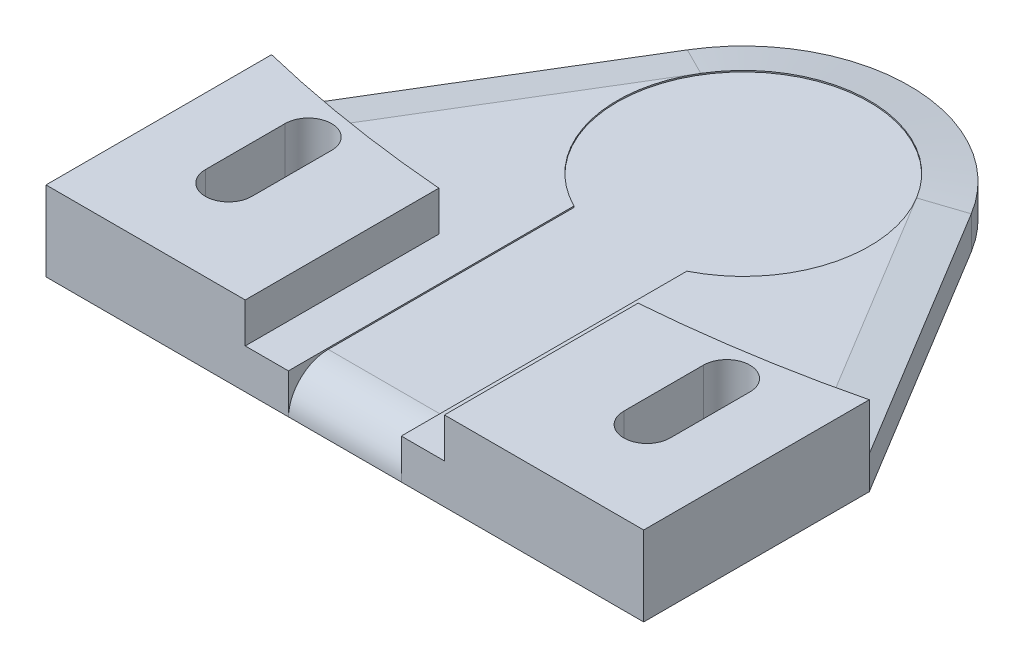
SolidWorks part; units mm, degrees
ref_plane "Front Plane" through (0, 0, 0) normal (0, 0, 1) x (1, 0, 0)
ref_plane "Top Plane" through (0, 0, 0) normal (0, 1, 0) x (1, 0, 0)
ref_plane "Right Plane" through (0, 0, 0) normal (1, 0, 0) x (0, 0, -1)
sketch "Sketch1" plane through (0, 0, 0) normal (0, 1, 0) x (1, 0, 0)
  line L0 (-10.1, 97.6) -> (-5.1, 97.6) construction
  line L1 (-9.1, 105.2) -> (-3.5, 105.2) construction
  line L2 (-10.1, 104.2) -> (-10.1, 97.6) construction
  line L3 (-9.1, 85) -> (-3.5, 85) construction
  line L4 (10.1, 104.2) -> (10.1, 97.6) construction
  line L5 (-5.1, 97.6) -> (-5.1, 92.6) construction
  line L6 (-5.1, 92.6) -> (-10.1, 92.6) construction
  line L7 (-10.1, 92.6) -> (-10.1, 86) construction
  line L8 (10.1, 97.6) -> (5.1, 97.6) construction
  line L9 (5.1, 97.6) -> (5.1, 92.6) construction
  line L10 (5.1, 92.6) -> (10.1, 92.6) construction
  line L11 (10.1, 92.6) -> (10.1, 86) construction
  line L12 (-34.641, 100) -> (-17.3205, 90) construction
  line L13 (0, 80) -> (17.3205, 90) construction
  line L14 (0, 95.1) -> (0, 0) construction
  line L15 (-17.3205, 90) -> (-53.6936, 27) construction
  line L16 (-17.3205, 90) -> (0, 80) construction
  line L17 (17.3205, 90) -> (53.6936, 27) construction
  line L18 (17.3205, 90) -> (34.641, 100) construction
  line L19 (-53.6936, 27) -> (-50.2295, 25) construction
  line L20 (-50.2295, 25) -> (-41.5692, 40) construction
  line L21 (-32.909, 45) -> (32.909, 45) construction
  line L22 (41.5692, 40) -> (50.2295, 25) construction
  line L23 (50.2295, 25) -> (53.6936, 27) construction
  line L24 (-20.4959, 76.5) -> (-32.0429, 56.5) construction
  line L25 (-27.7128, 49) -> (27.7128, 49) construction
  line L26 (32.0429, 56.5) -> (20.4959, 76.5) construction
  line L27 (-16.1658, 79) -> (16.1658, 79) construction
  line L28 (-2.5, 104.2) -> (-2.5, 103.95) construction
  line L29 (-2.5, 103.95) -> (2.5, 103.95) construction
  line L30 (2.5, 103.95) -> (2.5, 104.2) construction
  line L31 (3.5, 105.2) -> (9.1, 105.2) construction
  line L32 (-2.5, 86) -> (-2.5, 86.25) construction
  line L33 (-2.5, 86.25) -> (2.5, 86.25) construction
  line L34 (2.5, 86.25) -> (2.5, 86) construction
  line L35 (3.5, 85) -> (9.1, 85) construction
  line L36 (-34.641, 100) -> (-20.6443, 112.1724) construction
  line L37 (-7.5199, 117.081) -> (7.5199, 117.081) construction
  line L38 (20.6443, 112.1724) -> (34.641, 100) construction
  line L39 (140.292, -127.8992) -> (137.792, -132.2294) construction
  line L40 (146.3738, -132.5653) -> (143.5738, -137.415) construction
  line L41 (146.0078, -131.1992) -> (140.292, -127.8992) construction
  line L42 (128.8801, -122.4653) -> (126.0801, -127.315) construction
  line L43 (135.9078, -148.693) -> (130.192, -145.393) construction
  line L44 (137.792, -132.2294) -> (133.4619, -129.7294) construction
  line L45 (133.4619, -129.7294) -> (135.9619, -125.3992) construction
  line L46 (135.9619, -125.3992) -> (130.2462, -122.0992) construction
  line L47 (130.192, -145.393) -> (132.692, -141.0628) construction
  line L48 (132.692, -141.0628) -> (128.3619, -138.5628) construction
  line L49 (128.3619, -138.5628) -> (125.8619, -142.893) construction
  line L50 (125.8619, -142.893) -> (120.1462, -139.593) construction
  line L51 (154.641, -107.8461) -> (137.3205, -117.8461) construction
  line L52 (120, -127.8461) -> (120, -147.8461) construction
  line L53 (137.3205, -117.8461) -> (100.9474, -54.8461) construction
  line L54 (137.3205, -117.8461) -> (120, -127.8461) construction
  line L55 (120, -147.8461) -> (47.2539, -147.8461) construction
  line L56 (120, -147.8461) -> (120, -167.8461) construction
  line L57 (100.9474, -54.8461) -> (97.4833, -56.8461) construction
  line L58 (97.4833, -56.8461) -> (106.1436, -71.8461) construction
  line L59 (106.1436, -81.8461) -> (73.2346, -138.8461) construction
  line L60 (64.5744, -143.8461) -> (47.2539, -143.8461) construction
  line L61 (47.2539, -143.8461) -> (47.2539, -147.8461) construction
  line L62 (127.2169, -108.3461) -> (115.6699, -88.3461) construction
  line L63 (107.0096, -88.3461) -> (79.2968, -136.3461) construction
  line L64 (83.6269, -143.8461) -> (106.7209, -143.8461) construction
  line L65 (127.2169, -113.3461) -> (111.0511, -141.3461) construction
  line L66 (142.2078, -137.781) -> (141.9913, -137.656) construction
  line L67 (141.9913, -137.656) -> (139.4913, -141.9862) construction
  line L68 (139.4913, -141.9862) -> (139.7078, -142.1112) construction
  line L69 (140.0738, -143.4772) -> (137.2738, -148.3269) construction
  line L70 (126.4462, -128.681) -> (126.6627, -128.806) construction
  line L71 (126.6627, -128.806) -> (124.1627, -133.1362) construction
  line L72 (124.1627, -133.1362) -> (123.9462, -133.0112) construction
  line L73 (122.5801, -133.3772) -> (119.7801, -138.2269) construction
  line L74 (154.641, -107.8461) -> (158.1843, -126.0538) construction
  line L75 (155.873, -139.8742) -> (148.3531, -152.899) construction
  line L76 (137.54, -161.8108) -> (120, -167.8461) construction
  line L77 (-130.192, -145.393) -> (-132.692, -141.0628) construction
  line L78 (-137.2738, -148.3269) -> (-140.0738, -143.4772) construction
  line L79 (-135.9078, -148.693) -> (-130.192, -145.393) construction
  line L80 (-119.7801, -138.2269) -> (-122.5801, -133.3772) construction
  line L81 (-146.0078, -131.1992) -> (-140.292, -127.8992) construction
  line L82 (-132.692, -141.0628) -> (-128.3619, -138.5628) construction
  line L83 (-128.3619, -138.5628) -> (-125.8619, -142.893) construction
  line L84 (-125.8619, -142.893) -> (-120.1462, -139.593) construction
  line L85 (-140.292, -127.8992) -> (-137.792, -132.2294) construction
  line L86 (-137.792, -132.2294) -> (-133.4619, -129.7294) construction
  line L87 (-133.4619, -129.7294) -> (-135.9619, -125.3992) construction
  line L88 (-135.9619, -125.3992) -> (-130.2462, -122.0992) construction
  line L89 (-120, -167.8461) -> (-120, -147.8461) construction
  line L90 (-120, -127.8461) -> (-137.3205, -117.8461) construction
  line L91 (-120, -147.8461) -> (-47.2539, -147.8461) construction
  line L92 (-120, -147.8461) -> (-120, -127.8461) construction
  line L93 (-137.3205, -117.8461) -> (-100.9474, -54.8461) construction
  line L94 (-137.3205, -117.8461) -> (-154.641, -107.8461) construction
  line L95 (-47.2539, -147.8461) -> (-47.2539, -143.8461) construction
  line L96 (-47.2539, -143.8461) -> (-64.5744, -143.8461) construction
  line L97 (-73.2346, -138.8461) -> (-106.1436, -81.8461) construction
  line L98 (-106.1436, -71.8461) -> (-97.4833, -56.8461) construction
  line L99 (-97.4833, -56.8461) -> (-100.9474, -54.8461) construction
  line L100 (-106.7209, -143.8461) -> (-83.6269, -143.8461) construction
  line L101 (-79.2968, -136.3461) -> (-107.0096, -88.3461) construction
  line L102 (-115.6699, -88.3461) -> (-127.2169, -108.3461) construction
  line L103 (-111.0511, -141.3461) -> (-127.2169, -113.3461) construction
  line L104 (-139.7078, -142.1112) -> (-139.4913, -141.9862) construction
  line L105 (-139.4913, -141.9862) -> (-141.9913, -137.656) construction
  line L106 (-141.9913, -137.656) -> (-142.2078, -137.781) construction
  line L107 (-143.5738, -137.415) -> (-146.3738, -132.5653) construction
  line L108 (-123.9462, -133.0112) -> (-124.1627, -133.1362) construction
  line L109 (-124.1627, -133.1362) -> (-126.6627, -128.806) construction
  line L110 (-126.6627, -128.806) -> (-126.4462, -128.681) construction
  line L111 (-126.0801, -127.315) -> (-128.8801, -122.4653) construction
  line L112 (-120, -167.8461) -> (-137.54, -161.8108) construction
  line L113 (-148.3531, -152.899) -> (-155.873, -139.8742) construction
  line L114 (-158.1843, -126.0538) -> (-154.641, -107.8461) construction
  line L115 (-34.641, 100) -> (-154.641, -107.8461) construction
  line L116 (154.641, -107.8461) -> (34.641, 100) construction
  line L117 (-120, -167.8461) -> (120, -167.8461) construction
  line L118 (22.5, -167.8461) -> (22.5, -150.8611)
  line L119 (-22.5, -167.8461) -> (-22.5, -150.8611)
  line L120 (-22.5, -167.8461) -> (22.5, -167.8461)
  line L122 (0, -167.8461) -> (0, -153.5641) construction
  line L123 (-120, -157.8461) -> (120, -157.8461) construction
  line L124 (-17.5, -154.8461) -> (-17.5, -160.8461)
  line L125 (-14, -154.8461) -> (-14, -160.8461)
  line L126 (14, -154.8461) -> (14, -160.8461)
  line L127 (17.5, -154.8461) -> (17.5, -160.8461)
  circle A0 centre (0, 0) radius 85 construction
  circle A1 centre (0, 95.1) radius 10.1 construction
  arc A2 (-9.1, 85) -> (-10.1, 86) centre (-9.1, 86) cw construction
  arc A3 (9.1, 85) -> (10.1, 86) centre (9.1, 86) ccw construction
  arc A4 (10.1, 104.2) -> (9.1, 105.2) centre (9.1, 104.2) ccw construction
  arc A5 (-9.1, 105.2) -> (-10.1, 104.2) centre (-9.1, 104.2) ccw construction
  arc A6 (34.641, 100) -> (-34.641, 100) centre (0, 80) ccw construction
  arc A7 (32.0429, 56.5) -> (27.7128, 49) centre (27.7128, 54) cw construction
  arc A8 (-27.7128, 49) -> (-32.0429, 56.5) centre (-27.7128, 54) cw construction
  arc A9 (20.4959, 76.5) -> (16.1658, 79) centre (16.1658, 74) ccw construction
  arc A10 (-16.1658, 79) -> (-20.4959, 76.5) centre (-16.1658, 74) ccw construction
  arc A11 (41.5692, 40) -> (32.909, 45) centre (32.909, 35) ccw construction
  arc A12 (-32.909, 45) -> (-41.5692, 40) centre (-32.909, 35) ccw construction
  arc A13 (3.5, 105.2) -> (2.5, 104.2) centre (3.5, 104.2) ccw construction
  arc A14 (-2.5, 104.2) -> (-3.5, 105.2) centre (-3.5, 104.2) ccw construction
  arc A15 (3.5, 85) -> (2.5, 86) centre (3.5, 86) cw construction
  arc A16 (-2.5, 86) -> (-3.5, 85) centre (-3.5, 86) cw construction
  arc A17 (20.6443, 112.1724) -> (7.5199, 117.081) centre (7.5199, 97.081) ccw construction
  arc A18 (-7.5199, 117.081) -> (-20.6443, 112.1724) centre (-7.5199, 97.081) ccw construction
  circle A19 centre (133.077, -135.3961) radius 10.1 construction
  arc A20 (128.8801, -122.4653) -> (130.2462, -122.0992) centre (129.7462, -122.9653) cw construction
  arc A21 (119.7801, -138.2269) -> (120.1462, -139.593) centre (120.6462, -138.7269) ccw construction
  arc A22 (135.9078, -148.693) -> (137.2738, -148.3269) centre (136.4078, -147.8269) ccw construction
  arc A23 (146.3738, -132.5653) -> (146.0078, -131.1992) centre (145.5078, -132.0653) ccw construction
  arc A24 (120, -167.8461) -> (154.641, -107.8461) centre (120, -127.8461) ccw construction
  arc A25 (83.6269, -143.8461) -> (79.2968, -136.3461) centre (83.6269, -138.8461) cw construction
  arc A26 (107.0096, -88.3461) -> (115.6699, -88.3461) centre (111.3397, -90.8461) cw construction
  arc A27 (106.7209, -143.8461) -> (111.0511, -141.3461) centre (106.7209, -138.8461) ccw construction
  arc A28 (127.2169, -113.3461) -> (127.2169, -108.3461) centre (122.8868, -110.8461) ccw construction
  arc A29 (64.5744, -143.8461) -> (73.2346, -138.8461) centre (64.5744, -133.8461) ccw construction
  arc A30 (106.1436, -81.8461) -> (106.1436, -71.8461) centre (97.4833, -76.8461) ccw construction
  arc A31 (140.0738, -143.4772) -> (139.7078, -142.1112) centre (139.2078, -142.9772) ccw construction
  arc A32 (142.2078, -137.781) -> (143.5738, -137.415) centre (142.7078, -136.915) ccw construction
  arc A33 (122.5801, -133.3772) -> (123.9462, -133.0112) centre (123.4462, -133.8772) cw construction
  arc A34 (126.4462, -128.681) -> (126.0801, -127.315) centre (126.9462, -127.815) cw construction
  arc A35 (137.54, -161.8108) -> (148.3531, -152.899) centre (131.0326, -142.899) ccw construction
  arc A36 (155.873, -139.8742) -> (158.1843, -126.0538) centre (138.5525, -129.8742) ccw construction
  circle A37 centre (-133.077, -135.3961) radius 10.1 construction
  arc A38 (-119.7801, -138.2269) -> (-120.1462, -139.593) centre (-120.6462, -138.7269) cw construction
  arc A39 (-128.8801, -122.4653) -> (-130.2462, -122.0992) centre (-129.7462, -122.9653) ccw construction
  arc A40 (-146.0078, -131.1992) -> (-146.3738, -132.5653) centre (-145.5078, -132.0653) ccw construction
  arc A41 (-137.2738, -148.3269) -> (-135.9078, -148.693) centre (-136.4078, -147.8269) ccw construction
  arc A42 (-154.641, -107.8461) -> (-120, -167.8461) centre (-120, -127.8461) ccw construction
  arc A43 (-115.6699, -88.3461) -> (-107.0096, -88.3461) centre (-111.3397, -90.8461) cw construction
  arc A44 (-79.2968, -136.3461) -> (-83.6269, -143.8461) centre (-83.6269, -138.8461) cw construction
  arc A45 (-127.2169, -108.3461) -> (-127.2169, -113.3461) centre (-122.8868, -110.8461) ccw construction
  arc A46 (-111.0511, -141.3461) -> (-106.7209, -143.8461) centre (-106.7209, -138.8461) ccw construction
  arc A47 (-106.1436, -71.8461) -> (-106.1436, -81.8461) centre (-97.4833, -76.8461) ccw construction
  arc A48 (-73.2346, -138.8461) -> (-64.5744, -143.8461) centre (-64.5744, -133.8461) ccw construction
  arc A49 (-143.5738, -137.415) -> (-142.2078, -137.781) centre (-142.7078, -136.915) ccw construction
  arc A50 (-139.7078, -142.1112) -> (-140.0738, -143.4772) centre (-139.2078, -142.9772) ccw construction
  arc A51 (-126.0801, -127.315) -> (-126.4462, -128.681) centre (-126.9462, -127.815) cw construction
  arc A52 (-123.9462, -133.0112) -> (-122.5801, -133.3772) centre (-123.4462, -133.8772) cw construction
  arc A53 (-158.1843, -126.0538) -> (-155.873, -139.8742) centre (-138.5525, -129.8742) ccw construction
  arc A54 (-148.3531, -152.899) -> (-137.54, -161.8108) centre (-131.0326, -142.899) ccw construction
  arc A55 (-22.5, -150.8611) -> (22.5, -150.8611) centre (0, -58.5641) ccw
  arc A56 (-14, -154.8461) -> (-17.5, -154.8461) centre (-15.75, -154.8461) ccw
  arc A57 (-17.5, -160.8461) -> (-14, -160.8461) centre (-15.75, -160.8461) ccw
  arc A58 (17.5, -160.8461) -> (14, -160.8461) centre (15.75, -160.8461) cw
  arc A59 (14, -154.8461) -> (17.5, -154.8461) centre (15.75, -154.8461) cw
  point P58 (2.5, 105.2)
  point P67 (2.5, 85)
  point P74 (15, 117.081)
  point P77 (-15, 117.081)
  point P222 (0, -58.5641)
  point P227 (0, -58.5641)
  dimension "D1" = 170
  dimension "D2" = 20.2
  dimension "D3" = 1
  dimension "D8" = 40
  dimension "D12" = 80
  dimension "D19" = 5
  dimension "D20" = 10
  dimension "D24" = 1
  dimension "D28" = 1
  dimension "D30" = 20
  dimension "D34" = 95
  dimension "D36" = 3.5
  dimension "D4" = 5
  dimension "D5" = 7.6
  dimension "D6" = 5
  dimension "D7" = 5
  dimension "D9" = 20
  dimension "D10" = 60
  dimension "D11" = 20
  dimension "D13" = 120
  dimension "D14" = 60
  dimension "D15" = 4
  dimension "D16" = 40
  dimension "D17" = 4
  dimension "D18" = 30
  dimension "D21" = 5
  dimension "D22" = 2.5
  dimension "D23" = 1.25
  dimension "D25" = 5
  dimension "D26" = 2.5
  dimension "D27" = 1.25
  dimension "D29" = 30
  dimension "D32" = 240
  dimension "D35" = 45
  dimension "D37" = 5
  dimension "D38" = 6
  dimension "D39" = 3
  dimension "D31" = 3
  dimension "D33" = 3
extrude "Boss-Extrude1" add sketch "Sketch1" along normal blind 6
sketch "Sketch2" plane through (0, 0, 0) normal (0, 1, 0) x (1, 0, 0)
  line L0 (22.5, -167.8461) -> (22.5, -150.8611) construction
  line L1 (-22.5, -167.8461) -> (22.5, -167.8461)
  line L2 (-22.5, -167.8461) -> (-22.5, -150.8611)
  line L3 (-22.5, -150.8611) -> (-10.691, -131.3691)
  line L4 (22.5, -167.8461) -> (22.5, -150.8611)
  line L5 (22.5, -150.8611) -> (10.691, -131.3691)
  line L6 (0, -167.8461) -> (0, -137.8461) construction
  line L7 (-17.5, -154.8461) -> (-17.5, -160.8461)
  line L8 (-14, -154.8461) -> (-14, -160.8461)
  line L9 (14, -154.8461) -> (14, -160.8461)
  line L10 (17.5, -154.8461) -> (17.5, -160.8461)
  arc A0 (10.691, -131.3691) -> (-10.691, -131.3691) centre (0, -137.8461) ccw
  arc A1 (-14, -154.8461) -> (-17.5, -154.8461) centre (-15.75, -154.8461) ccw
  arc A2 (-17.5, -160.8461) -> (-14, -160.8461) centre (-15.75, -160.8461) ccw
  arc A3 (-17.5, -160.8461) -> (-14, -160.8461) centre (-15.75, -160.8461) ccw construction
  arc A4 (-14, -154.8461) -> (-17.5, -154.8461) centre (-15.75, -154.8461) ccw construction
  arc A5 (17.5, -160.8461) -> (14, -160.8461) centre (15.75, -160.8461) cw
  arc A6 (14, -154.8461) -> (17.5, -154.8461) centre (15.75, -154.8461) cw
  dimension "D1" = 25
  dimension "D2" = 30
extrude "Boss-Extrude2" add sketch "Sketch2" along normal blind 3
sketch "Sketch3" plane through (0, 6, 0) normal (0, 1, 0) x (1, 0, 0)
  line L0 (-22.5, -167.8461) -> (22.5, -167.8461) construction
  line L1 (-7.5, -167.8461) -> (7.5, -167.8461)
  line L2 (-7.5, -167.8461) -> (-7.5, -153.2675)
  line L3 (-7.5, -153.2675) -> (7.5, -153.2675)
  line L4 (7.5, -167.8461) -> (7.5, -153.2675)
  line L5 (0, -153.2675) -> (0, -167.8461) construction
  arc A0 (-22.5, -150.8611) -> (22.5, -150.8611) centre (0, -58.5641) ccw construction
  dimension "D1" = 15
extrude "Cut-Extrude1" cut sketch "Sketch3" against normal blind 3
sketch "Sketch4" plane through (0, 3, 0) normal (0, 1, 0) x (1, 0, 0)
  line L0 (-4.25, -146.3424) -> (-4.25, -167.8461)
  line L1 (-7.5, -167.8461) -> (7.5, -167.8461) construction
  line L2 (-4.25, -167.8461) -> (4.25, -167.8461)
  line L3 (4.25, -167.8461) -> (4.25, -146.3424)
  arc A0 (4.25, -146.3424) -> (-4.25, -146.3424) centre (0, -137.8461) ccw
  arc A1 (10.691, -131.3691) -> (-10.691, -131.3691) centre (0, -137.8461) ccw construction
  dimension "D1" = 19
  dimension "D2" = 8.5
extrude "Cut-Extrude2" cut sketch "Sketch4" against normal blind 0.1
fillet "Fillet1" radius 3 1 edges at (0, 2.9, 167.8461)
chamfer "Chamfer1" distance 3 angle 10 3 edges at (16.5955, 3, 141.1151) (-16.5955, 3, 141.1151) (0, 3, 125.3461) first distance on face at (0, 3, 150.9705)
